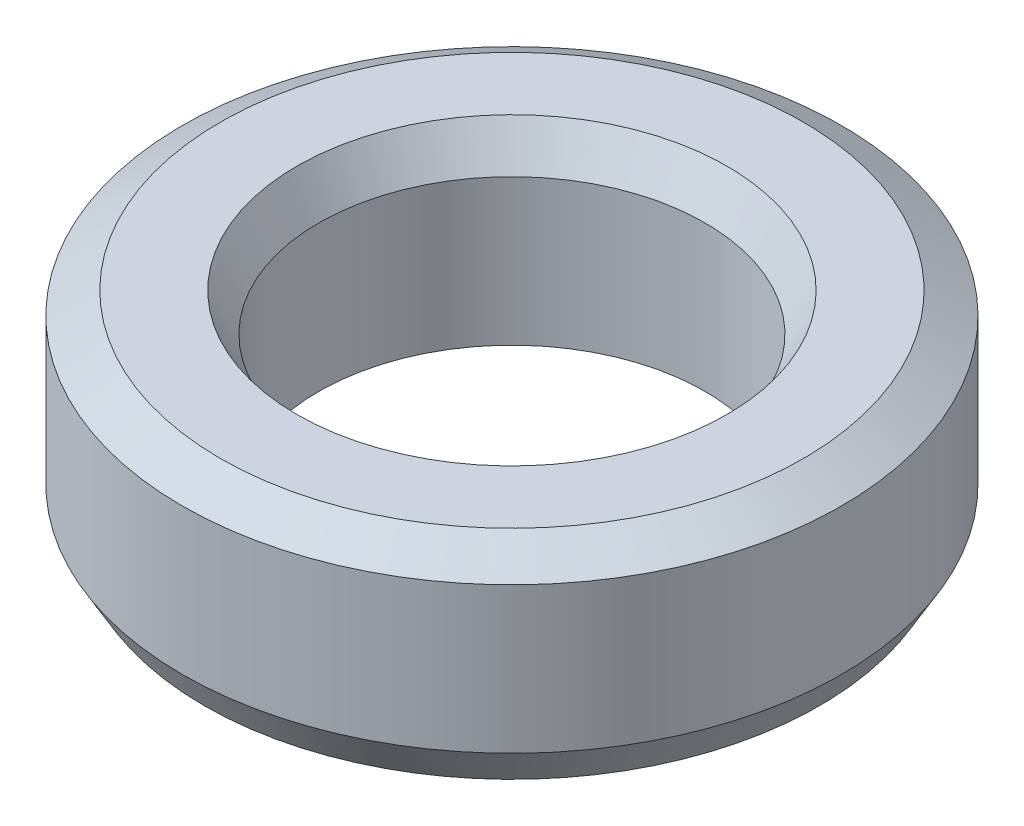
SolidWorks part; units mm, degrees
ref_plane "Front Plane" through (0, 0, 0) normal (0, 0, 1) x (1, 0, 0)
ref_plane "Top Plane" through (0, 0, 0) normal (0, 1, 0) x (1, 0, 0)
ref_plane "Right Plane" through (0, 0, 0) normal (1, 0, 0) x (0, 0, -1)
sketch "Sketch1" plane through (0, 0, 0) normal (0, 1, 0) x (1, 0, 0)
  circle A0 centre (0, 0) radius 55
  dimension "SLEEVE_OD" = 110
extrude "Boss-Extrude1" add sketch "Sketch1" along normal blind 34.3917
sketch "Sketch2" plane through (0, 0, 0) normal (0, 1, 0) x (1, 0, 0)
  circle A0 centre (0, 0) radius 32.2248
  dimension "BORE_D" = 64.4497
extrude "Cut-Extrude1" cut sketch "Sketch2" along normal through all
chamfer "Chamfer1" distance 3.6736 angle 60 4 edges at (0, 34.3917, 32.2248) (0, 0, 32.2248) (0, 0, 55) (0, 34.3917, 55) first distance on face at (0, 34.3917, 32.2248) first distance on face at (0, 0, 32.2248) first distance on face at (0, 34.3917, 55)
